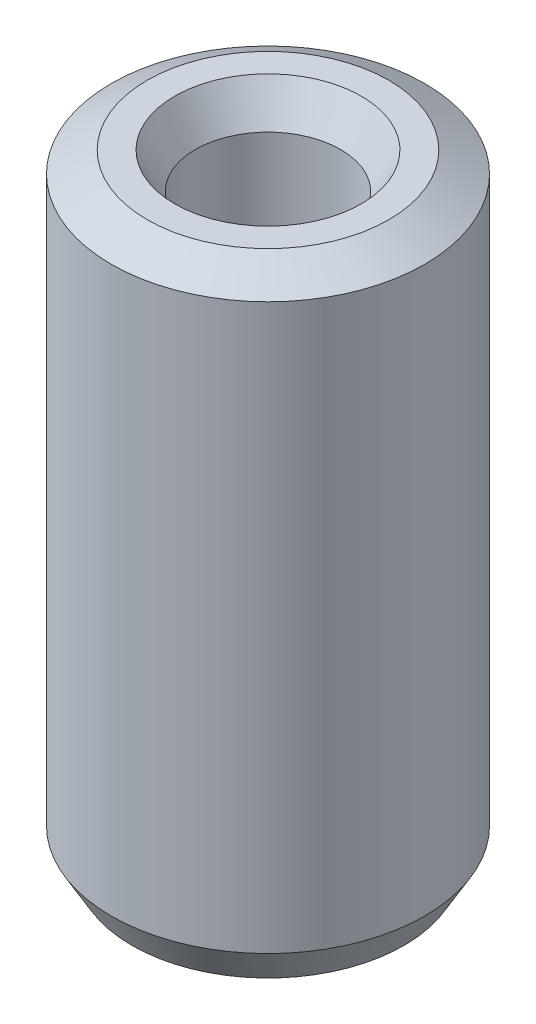
SolidWorks part; units mm, degrees
ref_plane "Front Plane" through (0, 0, 0) normal (0, 0, 1) x (1, 0, 0)
ref_plane "Top Plane" through (0, 0, 0) normal (0, 1, 0) x (1, 0, 0)
ref_plane "Right Plane" through (0, 0, 0) normal (1, 0, 0) x (0, 0, -1)
sketch "Sketch1" plane through (0, 0, 0) normal (0, 1, 0) x (1, 0, 0)
  circle A0 centre (0, 0) radius 22.5
  dimension "SLEEVE_OD" = 45
extrude "Boss-Extrude1" add sketch "Sketch1" along normal blind 89.1913
sketch "Sketch2" plane through (0, 0, 0) normal (0, 1, 0) x (1, 0, 0)
  circle A0 centre (0, 0) radius 10.4319
  dimension "BORE_D" = 20.8638
extrude "Cut-Extrude1" cut sketch "Sketch2" along normal through all
chamfer "Chamfer1" distance 2.9728 angle 60 4 edges at (0, 89.1913, 10.4319) (0, 0, 10.4319) (0, 0, 22.5) (0, 89.1913, 22.5) first distance on face at (0, 89.1913, 10.4319) first distance on face at (0, 0, 10.4319) first distance on face at (0, 89.1913, 22.5)
